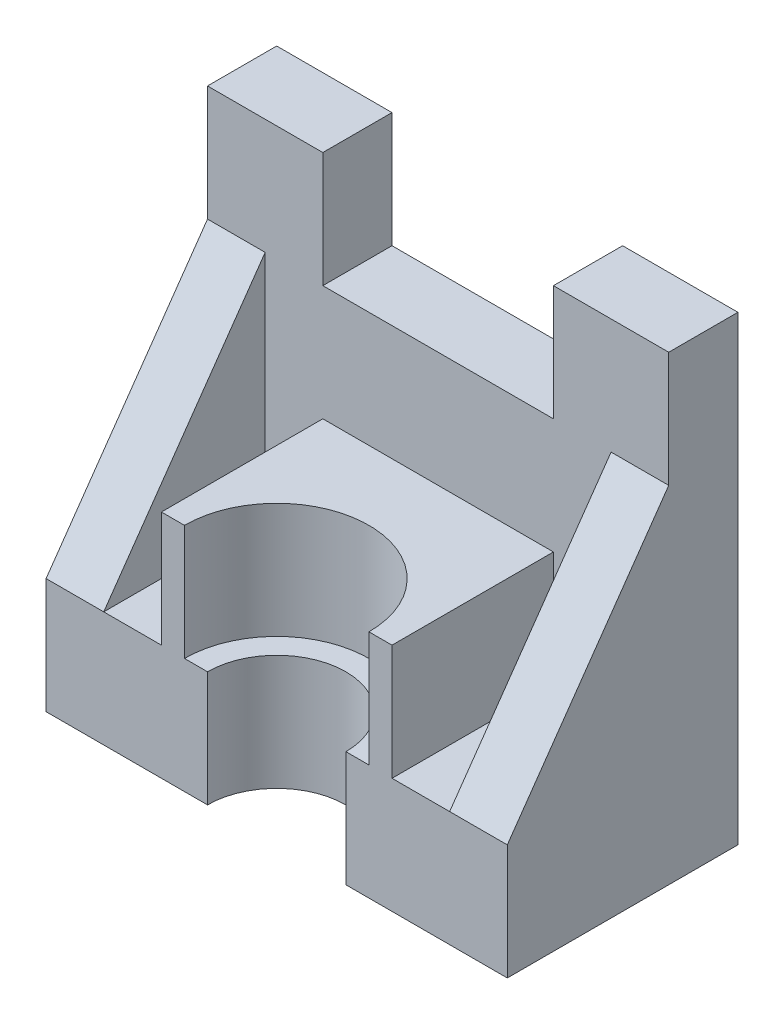
SolidWorks part; units mm, degrees
ref_plane "Front" through (0, 0, 0) normal (0, 0, 1) x (1, 0, 0)
ref_plane "Top" through (0, 0, 0) normal (0, 1, 0) x (1, 0, 0)
ref_plane "Right" through (0, 0, 0) normal (1, 0, 0) x (0, 0, -1)
sketch "Sketch1" plane through (0, 0, 0) normal (0, 0, 1) x (1, 0, 0)
  line L0 (-51.2399, -32.7147) -> (48.7601, -32.7147)
  line L1 (48.7601, -32.7147) -> (48.7601, -7.7147)
  line L2 (48.7601, -7.7147) -> (23.7601, -7.7147)
  line L3 (23.7601, -7.7147) -> (23.7601, 17.2853)
  line L4 (23.7601, 17.2853) -> (-26.2399, 17.2853)
  line L5 (-26.2399, 17.2853) -> (-26.2399, -7.7147)
  line L6 (-26.2399, -7.7147) -> (-51.2399, -7.7147)
  line L7 (-51.2399, -7.7147) -> (-51.2399, -32.7147)
  line L8 (48.7601, -7.7147) -> (48.7601, 67.2853)
  line L9 (48.7601, 67.2853) -> (23.7601, 67.2853)
  line L10 (23.7601, 67.2853) -> (23.7601, 42.2853)
  line L11 (23.7601, 42.2853) -> (-26.2399, 42.2853)
  line L12 (-26.2399, 42.2853) -> (-26.2399, 67.2853)
  line L13 (-26.2399, 67.2853) -> (-51.2399, 67.2853)
  line L14 (-51.2399, 67.2853) -> (-51.2399, -7.7147)
  line L15 (48.7601, -7.7147) -> (48.7601, 42.2853)
  line L16 (48.7601, 42.2853) -> (36.2601, 42.2853)
  line L17 (36.2601, 42.2853) -> (36.2601, -7.7147)
  line L18 (-51.2399, -7.7147) -> (-51.2399, 42.2853)
  line L19 (-51.2399, 42.2853) -> (-38.7399, 42.2853)
  line L20 (-38.7399, 42.2853) -> (-38.7399, -7.7147)
extrude "Boss-Extrude1" add sketch "Sketch1" along normal blind 50 contours L6 L7 L0 L1 L2 L3 L4 L5 | L20 L19 L14 L6 | L16 L17 L2 L8 region at (-1.2399, -11.8814, 0) region at (-44.9899, 17.2853, 0) region at (42.5101, 17.2853, 0)
extrude "Boss-Extrude2" add sketch "Sketch1<3>" along normal blind 15 contours L19 L20 L6 L5 L4 L3 L2 L17 L16 L8 L9 L10 L11 L12 L13 L14 region at (-1.2399, 33.9519, 0)
sketch "Sketch1<3>" plane through (0, 0, 0) normal (0, 0, 1) x (1, 0, 0) same geometry as "Sketch1"
sketch "Sketch3" plane through (0, 17.2853, 0) normal (0, 1, 0) x (1, 0, 0)
  line L0 (23.7601, -50) -> (-26.2399, -50) construction
  circle A0 centre (-1.2399, -50) radius 20
  circle A1 centre (-1.2399, -50) radius 15
extrude "Cut-Extrude3" cut sketch "Sketch3" against normal blind 150 contours A1
extrude "Cut-Extrude4" cut sketch "Sketch3<3>" against normal blind 25
sketch "Sketch3<3>" plane through (0, 17.2853, 0) normal (0, 1, 0) x (1, 0, 0) same geometry as "Sketch3"
sketch "Sketch6" plane through (48.7601, 0, 0) normal (1, 0, 0) x (0, 0, -1)
  line L0 (-50, -32.7147) -> (-50, -7.7147)
  line L1 (-50, -32.7147) -> (-50, 42.2853) construction
  line L2 (-50, -7.7147) -> (-15, 42.2853)
  line L3 (-15, 42.2853) -> (-50, 42.2853)
  line L4 (-50, 42.2853) -> (-50, -7.7147)
  line M4 (-15, 42.2853) -> (-50, 42.2853)
  line M5 (-50, 42.2853) -> (-50, -32.7147)
extrude "Cut-Extrude7" cut sketch "Sketch6" against normal blind 20 contours L2 M5 M4 region at (48.7601, 25.6186, 38.3333)
sketch "Sketch7" plane through (-38.7399, 0, 0) normal (1, 0, 0) x (0, 0, -1)
  line L0 (-50, -7.7147) -> (-15, 42.2853)
  line L1 (-15, 42.2853) -> (-50, 42.2853)
  line L2 (-50, 42.2853) -> (-50, -7.7147)
extrude "Cut-Extrude8" cut sketch "Sketch7" against normal blind 20
